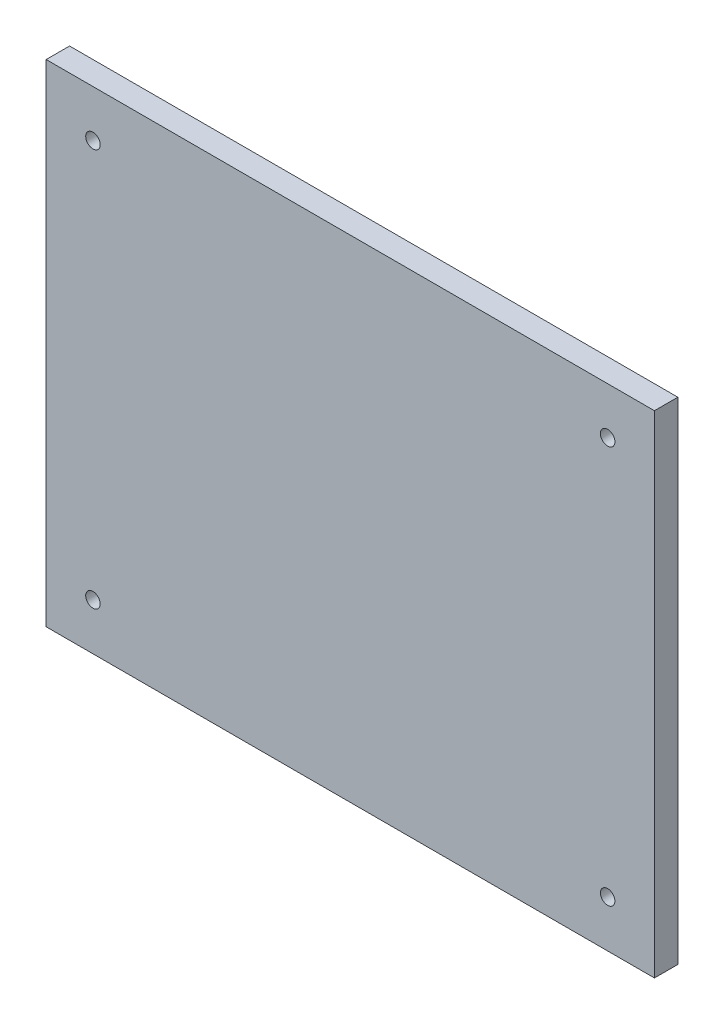
SolidWorks part; units mm, degrees
ref_plane "Plan de face" through (0, 0, 0) normal (0, 0, 1) x (1, 0, 0)
ref_plane "Plan de dessus" through (0, 0, 0) normal (0, 1, 0) x (1, 0, 0)
ref_plane "Plan de droite" through (0, 0, 0) normal (1, 0, 0) x (0, 0, -1)
sketch "Esquisse1" plane through (0, 0, 0) normal (0, 0, 1) x (1, 0, 0)
  line L0 (0, 0) -> (0, -21.9138) construction
  line L1 (-65, -52.5) -> (65, -52.5)
  line L2 (-65, -52.5) -> (-65, 52.5)
  line L3 (-65, 52.5) -> (65, 52.5)
  line L4 (65, -52.5) -> (65, 52.5)
  line L5 (-65, -52.5) -> (65, 52.5) construction
  line L6 (-65, 52.5) -> (65, -52.5) construction
  line L7 (0, 0) -> (-26.1988, 0) construction
  circle A1 centre (55, -42.5) radius 1.55
  circle A2 centre (-55, -42.5) radius 1.55
  circle A3 centre (-55, 42.5) radius 1.55
  circle A4 centre (55, 42.5) radius 1.55
  point P0 (0, 0)
  dimension "D3" = 3.1
  dimension "D1" = 130
  dimension "D2" = 105
  dimension "D4" = 10
  dimension "D5" = 10
extrude "Boss.-Extru.1" add sketch "Esquisse1" along normal blind 5
